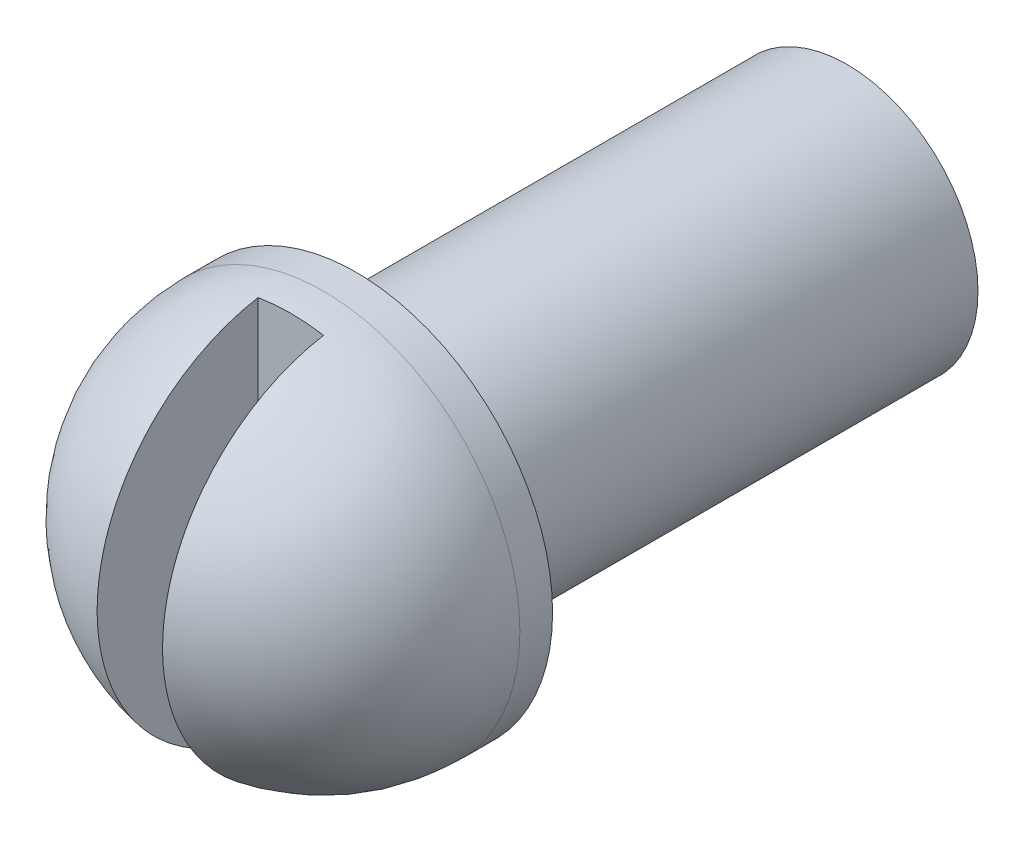
SolidWorks part; units mm, degrees
ref_plane "Front Plane" through (0, 0, 0) normal (0, 0, 1) x (1, 0, 0)
ref_plane "Top Plane" through (0, 0, 0) normal (0, 1, 0) x (1, 0, 0)
ref_plane "Right Plane" through (0, 0, 0) normal (1, 0, 0) x (0, 0, -1)
sketch "Sketch1" plane through (0, 0, 0) normal (0, 0, 1) x (1, 0, 0)
  circle A0 centre (0, 0) radius 4
  dimension "D1" = 8
extrude "Boss-Extrude1" add sketch "Sketch1" along normal blind 15
sketch "Sketch2" plane through (0, 0, 15) normal (0, 0, 1) x (1, 0, 0)
  circle A0 centre (0, 0) radius 6
  dimension "D1" = 12
extrude "Boss-Extrude2" add sketch "Sketch2" along normal blind 1
dome "Dome1" faces to dome 1 distance 6 reverse direction no elliptical dome no face at (6, 0, 16) parameters "D1"=6
ref_plane "Plane1" through (0, 0, 22) normal (0, 0, 1) x (1, 0, 0)
sketch "Sketch3" plane through (0, 0, 22) normal (0, 0, 1) x (1, 0, 0)
  line L1 (-1, 6.2398) -> (1, 6.2398)
  line L2 (-1, 6.2398) -> (-1, -6.6932)
  line L3 (-1, -6.6932) -> (1, -6.6932)
  line L4 (1, 6.2398) -> (1, -6.6932)
  dimension "D1" = 1
  dimension "D2" = 2
extrude "Cut-Extrude2" cut sketch "Sketch3" against normal blind 5
